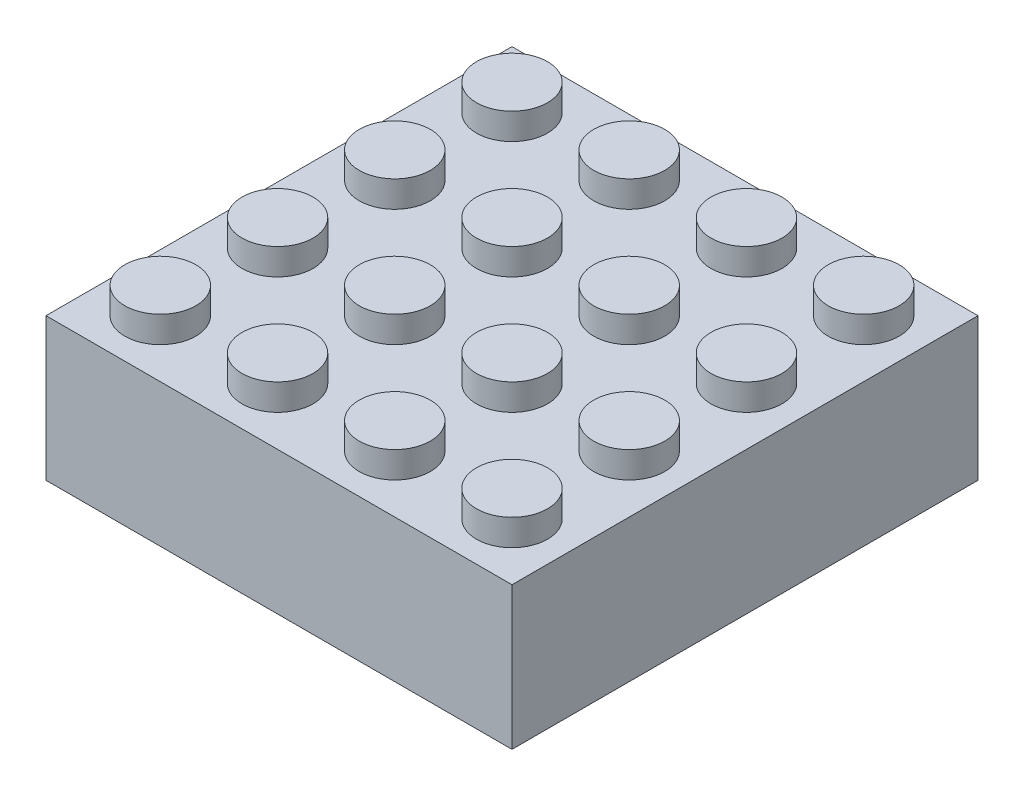
SolidWorks part; units mm, degrees
ref_plane "Front Plane" through (0, 0, 0) normal (0, 0, 1) x (1, 0, 0)
ref_plane "Top Plane" through (0, 0, 0) normal (0, 1, 0) x (1, 0, 0)
ref_plane "Right Plane" through (0, 0, 0) normal (1, 0, 0) x (0, 0, -1)
sketch "Sketch1" plane through (0, 0, 0) normal (0, 1, 0) x (1, 0, 0)
  line L1 (0, 0) -> (31.8, 0)
  line L2 (0, 0) -> (0, 31.8)
  line L3 (0, 31.8) -> (31.8, 31.8)
  line L4 (31.8, 0) -> (31.8, 31.8)
  dimension "D1" = 31.8
  dimension "D2" = 31.8
sketch "Sketch2" plane through (0, 0, 0) normal (0, 1, 0) x (1, 0, 0)
  line L0 (0, 0) -> (0, 31.8) construction
  line L1 (0, 31.8) -> (31.8, 31.8) construction
  circle A0 centre (3.9, 27.9) radius 2.425
  circle A1 centre (11.9, 27.9) radius 2.425
  circle A2 centre (19.9, 27.9) radius 2.425
  circle A3 centre (27.9, 27.9) radius 2.425
  circle A4 centre (11.9, 19.9) radius 2.425
  circle A5 centre (19.9, 19.9) radius 2.425
  circle A6 centre (27.9, 19.9) radius 2.425
  circle A7 centre (11.9, 11.9) radius 2.425
  circle A8 centre (19.9, 11.9) radius 2.425
  circle A9 centre (27.9, 11.9) radius 2.425
  circle A10 centre (11.9, 3.9) radius 2.425
  circle A11 centre (19.9, 3.9) radius 2.425
  circle A12 centre (27.9, 3.9) radius 2.425
  circle A13 centre (3.9, 19.9) radius 2.425
  circle A14 centre (3.9, 11.9) radius 2.425
  circle A15 centre (3.9, 3.9) radius 2.425
  dimension "D3" = 4.85
  dimension "D1" = 3.9
  dimension "D2" = 3.9
  dimension "D4" = 4
  dimension "D5" = 4
extrude "Boss-Extrude1" add sketch "Sketch2" along normal blind 1.8
extrude "Boss-Extrude2" add sketch "Sketch1" against normal blind 9.73
sketch "Sketch4" plane through (0, -9.73, 0) normal (0, -1, 0) x (1, 0, 0)
  line L1 (26.0857, -15.8744) -> (21.0164, -7.0925)
  line L2 (21.0164, -7.0925) -> (10.8054, -7.0798)
  line L3 (10.8054, -7.0798) -> (5.7143, -15.9291)
  line L4 (5.7143, -15.9291) -> (10.8306, -24.7346)
  line L5 (10.8306, -24.7346) -> (21.0154, -24.7081)
  line L6 (21.0154, -24.7081) -> (26.0857, -15.8744)
  circle A0 centre (15.9, -15.9) radius 10.1858
  point P40 (15.9, -15.9)
  dimension "D1" = 20.3715
extrude "Cut-Extrude1" cut sketch "Sketch4" against normal blind 6.63 contours L6 L1 L2 L3 L4 L5 region at (15.9038, -9.73, -15.9011)
sketch "Sketch9" plane through (0, -9.73, 0) normal (0, -1, 0) x (1, 0, 0)
  line L0 (21.0164, -7.0925) -> (10.8054, -7.0798) construction
  line L2 (11.8054, -7.0811) -> (20.0165, -7.0811)
  line L3 (11.8054, -7.0811) -> (11.8054, -5.3311)
  line L4 (11.8054, -5.3311) -> (20.0165, -5.3311)
  line L5 (20.0165, -7.0811) -> (20.0165, -5.3311)
  dimension "D1" = 1
  dimension "D2" = 1
  dimension "D3" = 1.75
extrude "Boss-Extrude4" add sketch "Sketch9" along normal blind 1.5
sketch "Sketch10" plane through (20.0165, 0, 0) normal (1, 0, 0) x (0, 0, -1)
  line L2 (7.0811, -11.23) -> (7.9811, -9.83)
  line L4 (7.9811, -9.83) -> (7.0811, -9.73)
  line L5 (7.0811, -11.23) -> (7.0811, -9.73)
  dimension "D3" = 1.4
  dimension "D4" = 0.9
extrude "Boss-Extrude5" add sketch "Sketch10" against normal up to surface (8.211 mm away) up to face at (11.8054, -10.48, -6.2061)
sketch "Sketch11" plane through (20.0165, 0, 0) normal (1, 0, 0) x (0, 0, -1)
  line L0 (6.3311, -11.23) -> (5.3311, -9.73)
  line L1 (7.0811, -11.23) -> (5.3311, -11.23) construction
  line L2 (5.3311, -9.73) -> (5.3311, -11.23)
  line L3 (5.3311, -11.23) -> (6.3311, -11.23)
  dimension "D1" = 1
extrude "Cut-Extrude4" cut sketch "Sketch11" against normal up to next (8.211 mm away)
ref_axis "Axis2" through (15.9, 33.0797, -15.9) along (0, -1, 0)
pattern_circular "CirPattern3" count 6 over 360 about axis through (15.9, 33.0797, -15.9) along (0, -1, 0) of "Boss-Extrude4", "Boss-Extrude5", "Cut-Extrude4"
